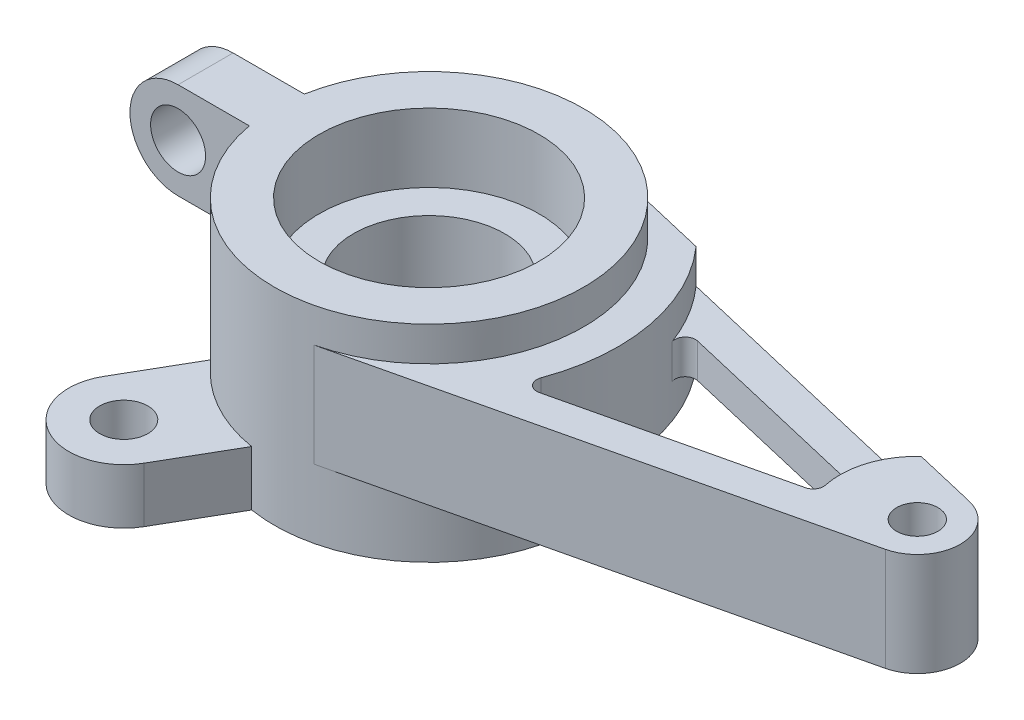
SolidWorks part; units mm, degrees
ref_plane "Front Plane" through (0, 0, 0) normal (0, 0, 1) x (1, 0, 0)
ref_plane "Top Plane" through (0, 0, 0) normal (0, 1, 0) x (1, 0, 0)
ref_plane "Right Plane" through (0, 0, 0) normal (1, 0, 0) x (0, 0, -1)
sketch "Sketch1" plane through (0, 0, 0) normal (0, 1, 0) x (1, 0, 0)
  circle A0 centre (0, 0) radius 4.5
  dimension "D1" = 4.5
extrude "Boss-Extrude1" add sketch "Sketch1" along normal blind 6
sketch "Sketch3" plane through (0, 0, 0) normal (0, -1, 0) x (1, 0, 0)
  line L0 (0, 0) -> (0, 8.8595) construction
  line L1 (0, 0) -> (-6.4052, 0) construction
  line L2 (0, 0) -> (-3.25, 5.6292) construction
  line L3 (-4.6356, 4.8292) -> (-3.4886, 2.8425)
  line L4 (-1.8644, 6.4292) -> (-0.7173, 4.4425)
  line L5 (-1.8644, -6.4292) -> (-0.7173, -4.4425)
  line L6 (-4.6356, -4.8292) -> (-3.4886, -2.8425)
  circle A0 centre (-3.25, 5.6292) radius 0.7
  circle A1 centre (-3.25, 5.6292) radius 1.6
  circle A2 centre (0, 0) radius 4.5 construction
  circle A3 centre (0, 0) radius 4.5
  circle A4 centre (-3.25, -5.6292) radius 1.6
  circle A5 centre (-3.25, -5.6292) radius 0.7
  point P9 (0, 0)
  circle M1 centre (0, 0) radius 4.5
  dimension "D1" = 1.6
  dimension "D2" = 0.7
  dimension "D3" = 30
  dimension "D4" = 6.5
extrude "Boss-Extrude2" add sketch "Sketch3" against normal blind 1.6 contours A1 A0 | A1 L3 L4 M1 | A4 A5 | L6 A4 L5 M1 region at (-2.4474, 0, 4.2389) region at (-4.0274, 0, 6.9756) region at (-2.4474, 0, -4.2389) region at (-2.8476, 0, -4.1274)
sketch "Sketch4" plane through (0, 0, 0) normal (0, 0, 1) x (1, 0, 0)
  line L0 (-3.5, 6) -> (-6.5, 6)
  line L1 (4.5, 6) -> (-4.5, 6) construction
  line L2 (-6.5, 3.2) -> (-3.5, 3.2)
  line L4 (-3.5, 3.2) -> (-3.5, 6)
  arc A0 (-6.5, 6) -> (-6.5, 3.2) centre (-6.5, 4.6) ccw
  circle A1 centre (-6.5, 4.6) radius 0.8
  point P7 (0, 0)
  dimension "D1" = 1.6
  dimension "D2" = 1.4
  dimension "D3" = 6.5
  dimension "D4" = 3
extrude "Boss-Extrude3" add sketch "Sketch4" along normal mid plane 1.6
sketch "Sketch5" plane through (0, 6, 0) normal (0, 1, 0) x (1, 0, 0)
  line L0 (0, 0) -> (14.2, 0) construction
  line L1 (1.0299, 4.3806) -> (14.4861, 1.2168)
  line L2 (1.0299, -4.3806) -> (14.4861, -1.2168)
  line L3 (4.9311, 2.4361) -> (12.0805, 0.7551)
  line L5 (0.8011, 3.4071) -> (14.2572, 0.2434) construction
  line L6 (4.9311, -2.4361) -> (12.0805, -0.7551)
  line L7 (0.8011, -3.4071) -> (14.2572, -0.2434) construction
  circle A0 centre (14.2, 0) radius 0.6
  arc A1 (12.6649, 1.645) -> (12.0805, -0.7551) centre (14.2, 0) ccw
  arc A2 (14.4861, -1.2168) -> (14.4861, 1.2168) centre (14.2, 0) ccw
  arc A3 (-4.4283, -0.8) -> (-4.4283, 0.8) centre (0, 0) ccw construction
  arc A4 (-4.4283, -0.8) -> (-4.4283, 0.8) centre (0, 0) ccw
  arc A5 (4.9311, -2.4361) -> (4.1083, 3.6568) centre (0, 0) ccw
  arc A7 (14.2572, -0.2434) -> (14.2572, 0.2434) centre (14.2, 0) ccw construction
  arc M1 (-4.4283, -0.8) -> (-4.4283, 0.8) centre (0, 0) ccw
  dimension "D2" = 4.5
  dimension "D3" = 2.5
  dimension "D4" = 1.2
  dimension "D5" = 11
  dimension "D1" = 14.2
  dimension "D6" = 1
extrude "Boss-Extrude4" add sketch "Sketch5" against normal blind 3 from offset 1 contours L6 A5 L1 L2 A2 A1 A0 M1 | A5 L3 A1 L1 region at (2.5305, 6, -3.8544) region at (8.446, 6, -2.1387) offset against normal yes
extrude "Cut-Extrude1" cut sketch "Sketch5<3>" against normal blind 1 from offset 1 contours A5 L3 A1 L1 region at (8.446, 6, -2.1387) offset against normal yes
sketch "Sketch5<3>" plane through (0, 6, 0) normal (0, 1, 0) x (1, 0, 0) same geometry as "Sketch5"
extrude "Cut-Extrude2" cut sketch "Sketch5<4>" against normal blind 1 from offset 3 contours A5 L3 A1 L1 region at (8.446, 6, -2.1387) offset against normal yes
sketch "Sketch5<4>" plane through (0, 6, 0) normal (0, 1, 0) x (1, 0, 0) same geometry as "Sketch5"
fillet "Fillet1" radius 0.3 4 edges at (4.9311, 3.5, -2.4361) (12.0805, 3.5, -0.7551) (12.0805, 3.5, 0.7551) (4.9311, 3.5, 2.4361)
sketch "Sketch6" plane through (0, 6, 0) normal (0, 1, 0) x (1, 0, 0)
  circle A0 centre (0, 0) radius 3.2
  circle A1 centre (0, 0) radius 2.2
  dimension "D1" = 6.4
  dimension "D2" = 4.4
extrude "Cut-Extrude4" cut sketch "Sketch6" against normal blind 2 contours A0 A1 region at (-3.1095, 6, 0)
extrude "Cut-Extrude5" cut sketch "Sketch6<4>" against normal through all contours A1 region at (0, 6, 0)
sketch "Sketch6<4>" plane through (0, 6, 0) normal (0, 1, 0) x (1, 0, 0) same geometry as "Sketch6"
